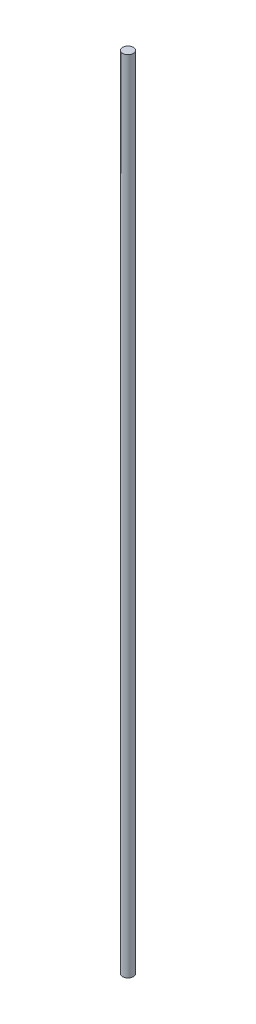
SolidWorks part; units mm, degrees
ref_plane "Front Plane" through (0, 0, 0) normal (0, 0, 1) x (1, 0, 0)
ref_plane "Top Plane" through (0, 0, 0) normal (0, 1, 0) x (1, 0, 0)
ref_plane "Right Plane" through (0, 0, 0) normal (1, 0, 0) x (0, 0, -1)
sketch "Sketch1" plane through (0, 0, 0) normal (0, 1, 0) x (1, 0, 0)
  circle A0 centre (0, 0) radius 8
extrude "Boss-Extrude1" add sketch "Sketch1" along normal blind 1200
